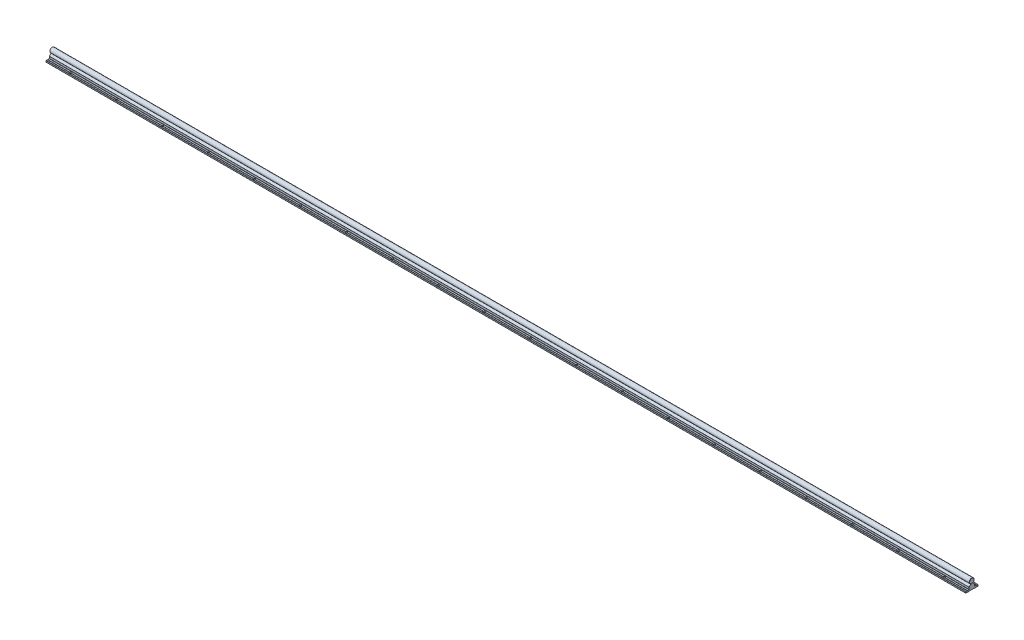
SolidWorks part; units mm, degrees
note: The reader was unsure of these and kept them because the rebuilt part matched: shared geometry of "Эскиз1<3>".
ref_plane "Спереди" through (0, 0, 0) normal (0, 0, 1) x (1, 0, 0)
ref_plane "Сверху" through (0, 0, 0) normal (0, 1, 0) x (1, 0, 0)
ref_plane "Справа" through (0, 0, 0) normal (1, 0, 0) x (0, 0, -1)
sketch "Эскиз1" plane through (0, 0, 0) normal (1, 0, 0) x (0, 0, -1)
  line L0 (0, 0) -> (0, -25) construction
  line L1 (0, -25) -> (-20, -25) construction
  line L2 (-4.75, -25) -> (-20, -25)
  line L3 (-20, -25) -> (-20, -20)
  line L4 (-20, -20) -> (-9.25, -20)
  line L5 (-9.25, -20) -> (-9.25, -13.3)
  line L6 (-9.25, -13.3) -> (-9.1101, -13.3)
  line L7 (-9.1101, -13.3) -> (-4, -7.21)
  line L8 (-4, -7.21) -> (-3.8, -7.21)
  line L9 (-3.8, -7.21) -> (0, -8.3557)
  line L10 (-2.75, -7.5266) -> (-2.75, -19) construction
  line L11 (-2.75, -19) -> (-4.75, -19) construction
  line L12 (-4.75, -19) -> (-4.75, -25) construction
  line L13 (-4.75, -25) -> (-4.75, -24.4)
  line L14 (-4.75, -24.4) -> (4.75, -24.4)
  line L15 (4.75, -25) -> (4.75, -24.4)
  line L16 (4.75, -25) -> (20, -25)
  line L17 (20, -25) -> (20, -20)
  line L18 (20, -20) -> (9.25, -20)
  line L19 (9.25, -20) -> (9.25, -13.3)
  line L20 (9.25, -13.3) -> (9.1101, -13.3)
  line L21 (9.1101, -13.3) -> (4, -7.21)
  line L22 (4, -7.21) -> (3.8, -7.21)
  line L23 (3.8, -7.21) -> (0, -8.3557)
  line L24 (-15, -20) -> (-15, -25) construction
  line L25 (-15.5, -20) -> (-15, -20.5)
  line L26 (-15, -20.5) -> (-14.5, -20)
  line L27 (15.5, -20) -> (15, -20.5)
  line L28 (15, -20) -> (15, -25) construction
  line L29 (15, -20.5) -> (14.5, -20)
  circle A0 centre (0, 0) radius 8
  point P17 (0, -24.4)
  point P37 (0, -10.2658)
  point P38 (0, -8.4592)
  dimension "D1" = 16
  dimension "D2" = 17.79
  dimension "D3" = 8
  dimension "D4" = 40
  dimension "D5" = 0.2
  dimension "D6" = 18.5
  dimension "D7" = 5
  dimension "D8" = 40
  dimension "D9" = 11.7
  dimension "D10" = 4.75
  dimension "D11" = 2.75
  dimension "D12" = 6
  dimension "D13" = 0.6
  dimension "D14" = 1
  dimension "D15" = 15
  dimension "D16" = 25
extrude "Опора" add sketch "Эскиз1" along normal mid plane 3000 contours L27 L29 L18 L19 L20 L21 L22 L23 L9 L8 L7 L6 L5 L4 L26 L25 L3 L2 L13 L14 L15 L16 L17
extrude "Вал" add sketch "Эскиз1<3>" along normal mid plane 3000 separate body contours A0
sketch "Эскиз1<3>" plane through (0, 0, 0) normal (1, 0, 0) x (0, 0, -1) same geometry as "Эскиз1"
fillet "Скругление4" radius 0.2 7 edges at (0, -20, -15.5) (0, -20, -14.5) (0, -20, 14.5) (0, -20, 15.5) (0, -8.3557, 0) (0, -24.4, -4.75) (0, -24.4, 4.75)
sketch "Эскиз2" plane through (0, -20, 0) normal (0, 1, 0) x (1, 0, 0)
  line L0 (-1425, 15) -> (-1425, -15) construction
  line L1 (1500, 15) -> (-1500, 15) construction
  line L2 (1500, -15) -> (-1500, -15) construction
  line L3 (-1500, 8) -> (-1500, -8) construction
  line L4 (-1275, 15) -> (-1275, -15) construction
  line L5 (-1125, 15) -> (-1125, -15) construction
  line L6 (-975, 15) -> (-975, -15) construction
  line L7 (-825, 15) -> (-825, -15) construction
  line L8 (-675, 15) -> (-675, -15) construction
  line L9 (-525, 15) -> (-525, -15) construction
  line L10 (-375, 15) -> (-375, -15) construction
  line L11 (-225, 15) -> (-225, -15) construction
  line L12 (-75, 15) -> (-75, -15) construction
  line L13 (75, 15) -> (75, -15) construction
  line L14 (225, 15) -> (225, -15) construction
  line L15 (375, 15) -> (375, -15) construction
  line L16 (525, 15) -> (525, -15) construction
  line L17 (675, 15) -> (675, -15) construction
  line L18 (825, 15) -> (825, -15) construction
  line L19 (975, 15) -> (975, -15) construction
  line L20 (1125, 15) -> (1125, -15) construction
  line L21 (1275, 15) -> (1275, -15) construction
  line L22 (1425, 15) -> (1425, -15) construction
  circle A0 centre (-1425, -15) radius 2.75
  circle A1 centre (-1425, 15) radius 2.75
  circle A2 centre (-1275, -15) radius 2.75
  circle A3 centre (-1275, 15) radius 2.75
  circle A4 centre (-1125, -15) radius 2.75
  circle A5 centre (-1125, 15) radius 2.75
  circle A6 centre (-975, -15) radius 2.75
  circle A7 centre (-975, 15) radius 2.75
  circle A8 centre (-825, -15) radius 2.75
  circle A9 centre (-825, 15) radius 2.75
  circle A10 centre (-675, -15) radius 2.75
  circle A11 centre (-675, 15) radius 2.75
  circle A12 centre (-525, -15) radius 2.75
  circle A13 centre (-525, 15) radius 2.75
  circle A14 centre (-375, -15) radius 2.75
  circle A15 centre (-375, 15) radius 2.75
  circle A16 centre (-225, -15) radius 2.75
  circle A17 centre (-225, 15) radius 2.75
  circle A18 centre (-75, -15) radius 2.75
  circle A19 centre (-75, 15) radius 2.75
  circle A20 centre (75, -15) radius 2.75
  circle A21 centre (75, 15) radius 2.75
  circle A22 centre (225, -15) radius 2.75
  circle A23 centre (225, 15) radius 2.75
  circle A24 centre (375, -15) radius 2.75
  circle A25 centre (375, 15) radius 2.75
  circle A26 centre (525, -15) radius 2.75
  circle A27 centre (525, 15) radius 2.75
  circle A28 centre (675, -15) radius 2.75
  circle A29 centre (675, 15) radius 2.75
  circle A30 centre (825, -15) radius 2.75
  circle A31 centre (825, 15) radius 2.75
  circle A32 centre (975, -15) radius 2.75
  circle A33 centre (975, 15) radius 2.75
  circle A34 centre (1125, -15) radius 2.75
  circle A35 centre (1125, 15) radius 2.75
  circle A36 centre (1275, -15) radius 2.75
  circle A37 centre (1275, 15) radius 2.75
  circle A38 centre (1425, -15) radius 2.75
  circle A39 centre (1425, 15) radius 2.75
  dimension "D1" = 5.5
  dimension "D2" = 5.5
  dimension "D6" = 5.5
  dimension "D7" = 5.5
  dimension "D3" = 75
  dimension "D5" = 150
  dimension "D4" = 20
extrude "Вырез-Вытянуть1" cut sketch "Эскиз2" against normal through all
sketch "Эскиз3" plane through (0, 0, 0) normal (0, 0, 1) x (1, 0, 0)
  line L0 (-1425, 56.4349) -> (-1425, -59.6123) construction
  line L1 (-1500, 8) -> (-1500, -8) construction
  line L2 (-1500, 0) -> (-1425, 0) construction
  line L3 (-1425, 0) -> (-1427.2, -1.2702)
  line L4 (-1427.2, -1.2702) -> (-1427.2, -7.5)
  line L5 (-1427.2, -7.5) -> (-1427.75, -7.5)
  line L6 (-1427.75, -7.5) -> (-1427.75, -19)
  line L7 (-1427.75, -19) -> (-1429.75, -19)
  line L8 (-1429.75, -19) -> (-1429.75, -24.4)
  line L9 (1500, -24.4) -> (-1500, -24.4) construction
  line L10 (-1429.75, -24.4) -> (-1425, -24.4)
  line L11 (-1425, -24.4) -> (-1425, 0)
  line L12 (1500, -25) -> (-1500, -25) construction
  point P20 (-1428.75, -19)
  dimension "D1" = 75
  dimension "D2" = 9.5
  dimension "D3" = 60
  dimension "D4" = 6
  dimension "D5" = 2.75
  dimension "D6" = 7.5
  dimension "D7" = 4.4
revolve "Вырез-Повернуть1" cut sketch "Эскиз3" angle 360 about L0
pattern_linear "Линейный массив1" count 20 spacing 150 along (1, 0, 0) of "Вырез-Повернуть1"
sketch "Эскиз4" plane through (0, 0, 0) normal (0, 0, 1) x (1, 0, 0)
  line L0 (-1425, 39.8402) -> (-1425, -50.2749) construction
  line L1 (-1500, 8) -> (-1500, -8) construction
  line L2 (-1500, 0) -> (-1425, 0) construction
  line L3 (-1425, -10) -> (-1427.2, -10)
  line L4 (-1427.2, -10) -> (-1427.2, -1.2702)
  line L5 (-1427.2, -1.2702) -> (-1425, 0)
  line L6 (-1425, 0) -> (-1425, -10)
  dimension "D1" = 75
  dimension "D2" = 60
  dimension "D3" = 2.2
  dimension "D4" = 10
revolve "Вырез-Повернуть2" cut sketch "Эскиз4" angle 360 about L0
pattern_linear "Линейный массив2" count 20 spacing 150 along (1, 0, 0) of "Вырез-Повернуть2"
sketch "Эскиз5" plane through (0, 0, 0) normal (0, 0, 1) x (1, 0, 0)
  line L0 (-1425, 35.5296) -> (-1425, -41.3293) construction
  line L1 (-1500, 8) -> (-1500, -8) construction
  line L2 (-1425, -24) -> (-1429.5, -24)
  line L3 (-1429.5, -24) -> (-1429.5, -19)
  line L4 (-1429.75, -19) -> (-1420.25, -19) construction
  line L5 (-1429.5, -19) -> (-1427.5, -19)
  line L6 (-1427.5, -19) -> (-1427.5, -2.4619)
  line L7 (-1427.5, -2.4619) -> (-1426.7, -2)
  line L8 (-1426.7, -2) -> (-1425, -2)
  line L9 (-1425, -2) -> (-1425, -24)
  dimension "D1" = 75
  dimension "D2" = 0.8
  dimension "D3" = 30
  dimension "D4" = 5
  dimension "D5" = 17
  dimension "D6" = 5
  dimension "D7" = 9
revolve "Повернуть1" add sketch "Эскиз5" angle 360 about L0
fillet "Скругление1" radius 0.3 1 edges at (-1425, -19, 4.5)
sketch "Эскиз6" plane through (0, -24, 0) normal (0, -1, 0) x (1, 0, 0)
  line L1 (-1423.25, -1.0104) -> (-1423.25, 1.0104)
  line L2 (-1423.25, 1.0104) -> (-1425, 2.0207)
  line L3 (-1425, 2.0207) -> (-1426.75, 1.0104)
  line L4 (-1426.75, 1.0104) -> (-1426.75, -1.0104)
  line L5 (-1426.75, -1.0104) -> (-1425, -2.0207)
  line L6 (-1425, -2.0207) -> (-1423.25, -1.0104)
  circle A0 centre (-1425, 0) radius 1.75 construction
  dimension "D1" = 3.5
extrude "Вырез-Вытянуть2" cut sketch "Эскиз6" against normal blind 3
fillet "Скругление2" radius 0.3 7 edges at (-1425, -24, 4.5) (-1423.25, -24, 0) (-1424.125, -24, 1.5155) (-1425.875, -24, 1.5155) (-1426.75, -24, 0) (-1425.875, -24, -1.5155) (-1424.125, -24, -1.5155)
pattern_linear "Линейный массив3" count 20 spacing 150 along (1, 0, 0) of bodies 114
chamfer "Фаска1" distance 0.5 angle 45 2 edges at (1500, 0, -8) (-1500, 0, -8)
fillet "Скругление3" radius 0.5 8 edges at (0, -20, -9.25) (0, -20, -20) (0, -25, -20) (0, -25, -4.75) (0, -25, 4.75) (0, -20, 9.25) (0, -25, 20) (0, -20, 20)
fillet "Скругление5" radius 0.2 4 edges at (0, -7.21, -3.8) (0, -7.21, -4) (0, -7.21, 4) (0, -7.21, 3.8)
fillet "Скругление6" radius 0.1 2 edges at (0, -13.3, -9.25) (0, -13.3, 9.25)
fillet "Скругление7" radius 0.1 2 edges at (0, -13.3, 9.1101) (0, -13.3, -9.1101)
